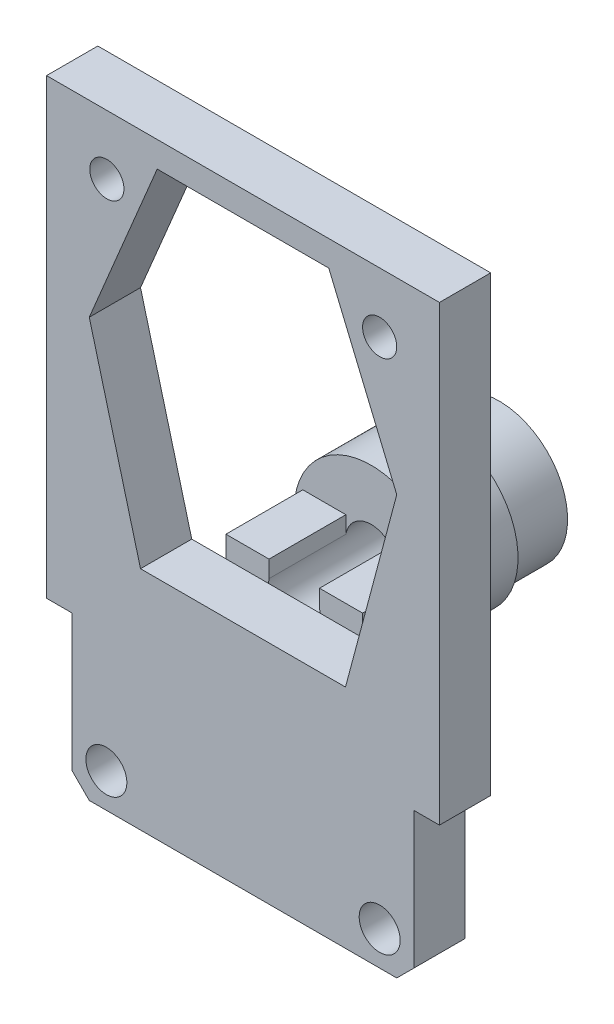
SolidWorks part; units mm, degrees
material "ABS"
ref_plane "Front Plane" through (0, 0, 0) normal (0, 0, 1) x (1, 0, 0)
ref_plane "Top Plane" through (0, 0, 0) normal (0, 1, 0) x (1, 0, 0)
ref_plane "Right Plane" through (0, 0, 0) normal (1, 0, 0) x (0, 0, -1)
sketch "Sketch1" plane through (0, 0, 0) normal (0, 0, 1) x (1, 0, 0)
  line L0 (0, 78.4471) -> (0, -76.9705) construction
  line L1 (-83.0616, 0) -> (77.155, 0) construction
  line L3 (-10, 5) -> (10, 5)
  line L4 (-10, 5) -> (-10, -5)
  line L5 (-10, -5) -> (10, -5)
  line L6 (10, 5) -> (10, -5)
  dimension "D1" = 20
  dimension "D2" = 10
extrude "Boss-Extrude1" add sketch "Sketch1" along normal blind 3
sketch "Sketch2" plane through (0, 0, 0) normal (0, 0, -1) x (-1, 0, 0)
  line L0 (0, -15.2672) -> (0, 42.8631) construction
  line L1 (4, 0) -> (-4, 0)
  line L2 (4, 0) -> (4, 9.5)
  line L3 (4, 9.5) -> (-4, 9.5)
  line L4 (-4, 0) -> (-4, 9.5)
  line L5 (-10, 5) -> (10, 5) construction
  dimension "D1" = 8
  dimension "D2" = 4.5
extrude "Boss-Extrude2" add sketch "Sketch2" along normal blind 6
sketch "Sketch3" plane through (0, 0, -6) normal (0, 0, -1) x (-1, 0, 0)
  line L0 (-4, 0) -> (4, 0) construction
  circle A0 centre (0, 8.25) radius 4.5
  dimension "D1" = 9
  dimension "D2" = 8.25
extrude "Boss-Extrude3" add sketch "Sketch3" along normal blind 6 and the other way blind 1.5
ref_plane "Plane1" through (0, 0, 3) normal (0, 0, 1) x (1, 0, 0)
hole_wizard "Ø3.0 (3) Diameter Hole1" positions "Sketch4" profile "Sketch5" hole size "Ø3.0" standard "ISO" end condition through all
sketch "Sketch4" plane through (0, 0, -12) normal (0, 0, -1) x (-1, 0, 0)
  circle A0 centre (0, 8.25) radius 4.5 construction
  point P0 (0, 8.25)
sketch "Sketch5" plane through (0, 8.25, -12) normal (1, 0, 0) x (0, 1, 0)
  line L0 (0, 0) -> (0, 15)
  line L1 (0, 15) -> (1.5, 15)
  line L2 (1.5, 15) -> (1.5, 0)
  line L5 (1.5, 0) -> (0, 0)
  line L11 (0, -6.35) -> (0, 107.95) construction
  dimension "Thru Hole Dia." = 3
  dimension "Thru Hole Depth" = 15
sketch "Sketch6" plane through (0, 0, 0) normal (0, 0, 1) x (1, 0, 0)
  line L0 (-1.4774, 8.5094) -> (-1.4774, 9.5)
  line L1 (-4, 9.5) -> (-0.8292, 9.5) construction
  line L2 (-1.4774, 9.5) -> (1.4774, 9.5)
  line L3 (1.4774, 9.5) -> (1.4774, 8.5094)
  line L4 (1.4774, 8.5094) -> (-1.4774, 8.5094)
  circle A0 centre (0, 8.25) radius 1.5 construction
extrude "Cut-Extrude1" cut sketch "Sketch6" against normal blind 4.5
chamfer "Chamfer1" distance 1 angle 45 4 edges at (-10, 5, 1.5) (10, 5, 1.5) (10, -5, 1.5) (-10, -5, 1.5)
sketch "Sketch7" plane through (0, 0, -6) normal (0, 0, -1) x (-1, 0, 0)
  line L0 (-4.5, 8.25) -> (-5.6094, 8.25)
  line L1 (-5.6094, 8.25) -> (-5.6094, 15.8966)
  line L2 (-5.6094, 15.8966) -> (5.7054, 15.8966)
  line L3 (5.7054, 15.8966) -> (5.7054, 8.25)
  line L4 (5.7054, 8.25) -> (4.5, 8.25)
  arc A0 (4.5, 8.25) -> (-4.5, 8.25) centre (0, 8.25) ccw
chamfer "Chamfer2" distance 1 angle 45 4 edges at (0, 0, -6) (0, 0, 0) (4, 2.5, 0) (-4, 2.5, 0)
chamfer "Chamfer3" distance 1 angle 45 1 edges at (0, 3.75, -6)
sketch "Sketch8" plane through (0, 0, -12) normal (0, 0, -1) x (-1, 0, 0)
  circle A0 centre (0, 8.25) radius 4
  circle A1 centre (0, 8.25) radius 4.5
  dimension "D1" = 8
extrude "Cut-Extrude3" cut sketch "Sketch8" against normal blind 3.4
chamfer "Chamfer4" distance 2 angle 45 1 edges at (0, 5, 0)
chamfer "Chamfer5" distance 2 angle 45 2 edges at (4, 5, 0.5) (-4, 5, 0.5)
hole_wizard "M2 Clearance Hole1" positions "Sketch9" profile "Sketch10" hole size "M2" standard "ISO" end condition through all
sketch "Sketch9" plane through (0, 0, 0) normal (0, 0, -1) x (-1, 0, 0)
  line L0 (0, 17.4642) -> (0, -12.0288) construction
  line L2 (-18.4305, -3) -> (19.5599, -3) construction
  line L4 (10, 4) -> (10, -4) construction
  line L5 (9, -5) -> (-9, -5) construction
  point P0 (8, -3)
  point P2 (-8, -3)
  dimension "D1" = 2
  dimension "D2" = 2
sketch "Sketch10" plane through (-8, -3, 0) normal (1, 0, 0) x (0, 1, 0)
  line L0 (0, 0) -> (0, 3)
  line L1 (0, 3) -> (1.2, 3)
  line L2 (1.2, 3) -> (1.2, 0)
  line L5 (1.2, 0) -> (0, 0)
  line L11 (0, -6.35) -> (0, 107.95) construction
  dimension "Thru Hole Dia." = 2.4
  dimension "Thru Hole Depth" = 3
ref_axis "Axis1" through (0, 8.25, -8.6) along (0, 0, -1)
hole_wizard "M1.6 Tapped Hole1" positions "Sketch11" profile "Sketch12" tap size "M1.6" standard "ISO"
sketch "Sketch11" plane through (0, 0, -12) normal (0, 0, -1) x (-1, 0, 0)
  line L0 (-5.1174, 8.25) -> (5.7056, 8.25) construction
  line L1 (0, 14.0942) -> (0, -5.7534) construction
  point P0 (2.75, 8.25)
  point P2 (-2.75, 8.25)
  dimension "D1" = 5.5
cosmetic thread "Hole Thread1" parameters "D1"=3.2, "D2"=1.6
cosmetic thread "Hole Thread2" parameters "D1"=3.2, "D2"=1.6
sketch "Sketch12" plane through (-2.75, 8.25, -12) normal (1, 0, 0) x (0, 1, 0)
  line L0 (0, 0) -> (0, 5.3755)
  line L1 (0, 5.3755) -> (0.625, 5)
  line L2 (0.625, 5) -> (0.625, 0)
  line L5 (0.625, 0) -> (0, 0)
  line L10 (0, 5.3755) -> (-0.625, 5) construction
  line L11 (0, -6.35) -> (0, 107.95) construction
  dimension "Tap Drill Dia." = 1.25
  dimension "Tap Drill Depth" = 5
  dimension "Drill Angle" = 118
sketch "Sketch13" plane through (0, 0, 3) normal (0, 0, 1) x (1, 0, 0)
  line L0 (-6, 8.25) -> (6, 8.25)
  line L3 (6, 8.25) -> (6, 5)
  line L5 (6, 5) -> (-6, 5)
  line L7 (-6, 5) -> (-6, 8.25)
extrude "Boss-Extrude5" add sketch "Sketch13" against normal up to surface (3 mm away) up to face at (-2.4018, 8.2826, 0)
sketch "Sketch14" plane through (0, 0, 0) normal (0, 0, -1) x (-1, 0, 0)
  line L0 (6, 8.25) -> (9, 19.5)
  line L1 (9, 19.5) -> (5.0227, 29)
  line L3 (5.0227, 29) -> (-5.0227, 29)
  line L4 (9, 19.5) -> (0, 19.5) construction
  line L5 (0, 29) -> (0, 8.25) construction
  line L6 (-1.5, 8.25) -> (1.5, 8.25) construction
  line L7 (6, 8.25) -> (1.5, 8.25)
  line L8 (10, 4) -> (10, 29)
  line L9 (10, 29) -> (5.0227, 29)
  line L10 (10, 4) -> (11.5, 4)
  line L11 (11.5, 4) -> (11.5, 30.5)
  line L12 (11.5, 30.5) -> (-11.5, 30.5)
  line L13 (0, 30.5) -> (0, 29)
  line L14 (6, 8.25) -> (6, 5)
  line L15 (6, 5) -> (9, 5)
  line L16 (9, 5) -> (10, 4)
  line L17 (-9, 5) -> (-10, 4)
  line L18 (-6, 5) -> (-9, 5)
  line L19 (-6, 8.25) -> (-6, 5)
  line L20 (-11.5, 4) -> (-11.5, 30.5)
  line L21 (-10, 4) -> (-11.5, 4)
  line L22 (-10, 29) -> (-5.0227, 29)
  line L23 (-10, 4) -> (-10, 29)
  line L24 (-6, 8.25) -> (-1.5, 8.25)
  line L25 (-9, 19.5) -> (-5.0227, 29)
  line L26 (-6, 8.25) -> (-9, 19.5)
  line M11 (9, 5) -> (6, 5)
  line M12 (6, 5) -> (6, 8.25)
  line M22 (-6, 8.25) -> (-6, 5)
  line M23 (-6, 5) -> (-9, 5)
  line M24 (-9, 5) -> (-10, 4)
  line M30 (10, 4) -> (9, 5)
  dimension "D1" = 1.5
  dimension "D2" = 1.5
  dimension "D3" = 9
extrude "Boss-Extrude6" add sketch "Sketch14" against normal up to vertex (3 mm away) contours L12 L13 L3 L9 L8 L10 L11 | L8 L9 L1 L0 M12 M11 M30 | L26 L25 L22 L23 M22 M24 M23 | L21 L23 L22 L3 L13 L12 L20 region at (-8.3685, 16.6456, 0) region at (-2.5113, 29.2889, 0) region at (2.5113, 29.2889, 0) region at (8.3685, 16.6456, 0) up to point (9, 5, 3)
sketch "Sketch15" plane through (0, 0, 3) normal (0, 0, 1) x (1, 0, 0)
  line L0 (-11.5, 4) -> (-10.2, 4)
  line L1 (10.2, 4) -> (11.5, 4)
  line L16 (10.2, 4) -> (10.2, 29.2)
  line L17 (10.2, 29.2) -> (-10.2, 29.2)
  line L18 (-10.2, 29.2) -> (-10.2, 4)
  line L21 (-11.5, 4) -> (-10, 4)
  line L22 (-11.5, 30.5) -> (-11.5, 4)
  line L23 (11.5, 30.5) -> (-11.5, 30.5)
  line L24 (11.5, 4) -> (11.5, 30.5)
  line L25 (10, 4) -> (11.5, 4)
  line L27 (-11.5, 30.5) -> (-11.5, 4)
  line L28 (11.5, 30.5) -> (-11.5, 30.5)
  line L29 (11.5, 4) -> (11.5, 30.5)
  dimension "D1" = 0
  dimension "D2" = 1.3
extrude "Boss-Extrude7" [suppressed] add sketch "Sketch15" along normal blind 4
sketch "Sketch16" plane through (0, 0, 3) normal (0, 0, 1) x (1, 0, 0)
  point P0 (8, 27)
  point P1 (-8, 27)
hole_wizard "Ø2.0mm Dowel Hole1" positions "Sketch17" profile "Sketch18" hole size "Ø2.0" standard "ISO" end condition through all
sketch "Sketch17" plane through (0, 0, 3) normal (0, 0, 1) x (1, 0, 0)
  point P0 (-7.9713, 27.0177)
  point P2 (8, 27)
sketch "Sketch18" plane through (-7.9713, 27.0177, 3) normal (1, 0, 0) x (0, -1, 0)
  line L0 (0, 0) -> (0, 15)
  line L1 (0, 15) -> (1, 15)
  line L2 (1, 15) -> (1, 0)
  line L5 (1, 0) -> (0, 0)
  line L11 (0, -6.35) -> (0, 107.95) construction
  dimension "Thru Hole Dia." = 2
  dimension "Thru Hole Depth" = 15
